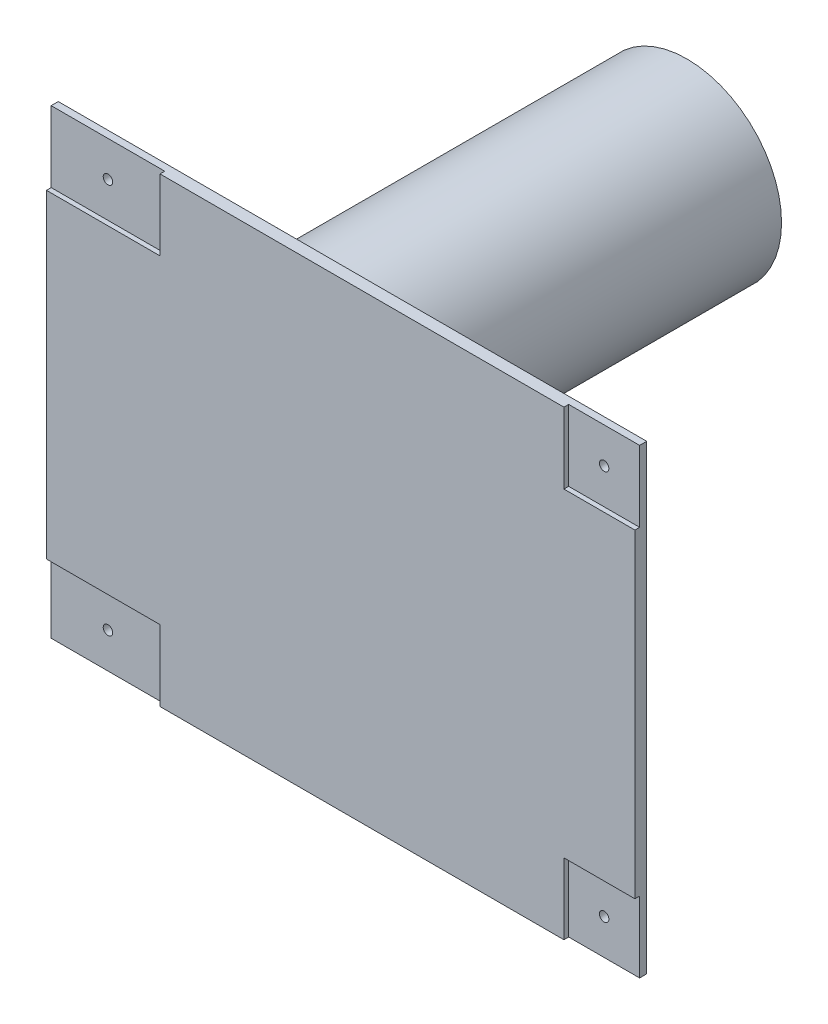
SolidWorks part; units mm, degrees
ref_plane "Alzado" through (0, 0, 0) normal (0, 0, 1) x (1, 0, 0)
ref_plane "Planta" through (0, 0, 0) normal (0, 1, 0) x (1, 0, 0)
ref_plane "Vista lateral" through (0, 0, 0) normal (1, 0, 0) x (0, 0, -1)
sketch "Croquis1" plane through (0, 0, 0) normal (0, 0, 1) x (1, 0, 0)
  line L1 (-117.2917, 97.7627) -> (131.4683, 97.7627)
  line L2 (-117.2917, 97.7627) -> (-117.2917, -97.2373)
  line L3 (-117.2917, -97.2373) -> (131.4683, -97.2373)
  line L4 (131.4683, 97.7627) -> (131.4683, -97.2373)
  dimension "D1" = 248.76
  dimension "D2" = 195
extrude "Saliente-Extruir1" add sketch "Croquis1" along normal blind 5
sketch "Croquis2" plane through (0, 0, 5) normal (0, 0, 1) x (1, 0, 0)
  line L0 (-117.2917, 0.2627) -> (131.4683, 0.2627) construction
  line L1 (-117.2917, 97.7627) -> (-117.2917, -97.2373) construction
  line L2 (131.4683, -97.2373) -> (131.4683, 97.7627) construction
  line L3 (-117.2917, -97.2373) -> (-69.2917, -97.2373)
  line L4 (-117.2917, -97.2373) -> (131.4683, -97.2373) construction
  line L5 (-69.2917, -97.2373) -> (-69.2917, -67.2373)
  line L6 (-69.2917, -67.2373) -> (-117.2917, -67.2373)
  line L7 (-117.2917, -67.2373) -> (-117.2917, -97.2373)
  line L8 (131.4683, 67.7627) -> (101.4683, 67.7627)
  line L9 (131.4683, -97.2373) -> (101.4683, -97.2373)
  line L10 (131.4683, -97.2373) -> (131.4683, -67.2373)
  line L11 (131.4683, -67.2373) -> (101.4683, -67.2373)
  line L12 (101.4683, -97.2373) -> (101.4683, -67.2373)
  line L13 (101.4683, 97.7627) -> (101.4683, 67.7627)
  line L14 (131.4683, 97.7627) -> (101.4683, 97.7627)
  line L15 (131.4683, 97.7627) -> (131.4683, 67.7627)
  line L16 (-69.2917, 67.7627) -> (-117.2917, 67.7627)
  line L17 (-69.2917, 97.7627) -> (-69.2917, 67.7627)
  line L18 (-117.2917, 97.7627) -> (-69.2917, 97.7627)
  line L19 (-117.2917, 67.7627) -> (-117.2917, 97.7627)
  dimension "D1" = 48
  dimension "D2" = 30
  dimension "D3" = 30
  dimension "D4" = 30
extrude "Cortar-Extruir1" cut sketch "Croquis2" against normal blind 2
sketch "Croquis3" plane through (0, 0, 5) normal (0, 0, 1) x (1, 0, 0)
  line L0 (-69.2917, 97.7627) -> (-117.2917, 97.7627) construction
  circle A0 centre (-93.2917, 82.7627) radius 2
  circle A1 centre (-93.2917, -82.2373) radius 2
  circle A2 centre (116.4683, 82.7627) radius 2
  circle A3 centre (116.4683, -82.2373) radius 2
  dimension "D2" = 4
  dimension "D3" = 4
  dimension "D5" = 4
  dimension "D6" = 4
  dimension "D1" = 15
  dimension "D4" = 15
  dimension "D7" = 209.76
  dimension "D8" = 165
extrude "Cortar-Extruir2" cut sketch "Croquis3" against normal blind 10
sketch "Croquis4" plane through (0, 0, 0) normal (0, 0, -1) x (-1, 0, 0)
  line L5 (-131.4683, -97.2373) -> (-131.4683, 97.7627) construction
  line L7 (-131.4683, 97.7627) -> (117.2917, 97.7627) construction
  circle A0 centre (57.5317, 0.2627) radius 40
  dimension "D3" = 80
  dimension "D1" = 189
  dimension "D2" = 97.5
extrude "Saliente-Extruir2" add sketch "Croquis4" along normal blind 206 contours A0
sketch "Croquis5" plane through (0, 0, 0) normal (0, 0, -1) x (-1, 0, 0)
  line L0 (-131.4683, 0.2627) -> (117.2917, 0.2627) construction
  line L1 (-131.4683, -97.2373) -> (-131.4683, 97.7627) construction
  line L2 (117.2917, 97.7627) -> (117.2917, -97.2373) construction
  circle A0 centre (-76.9683, 0.2627) radius 10.65
  dimension "D1" = 21.3
  dimension "D2" = 54.5
